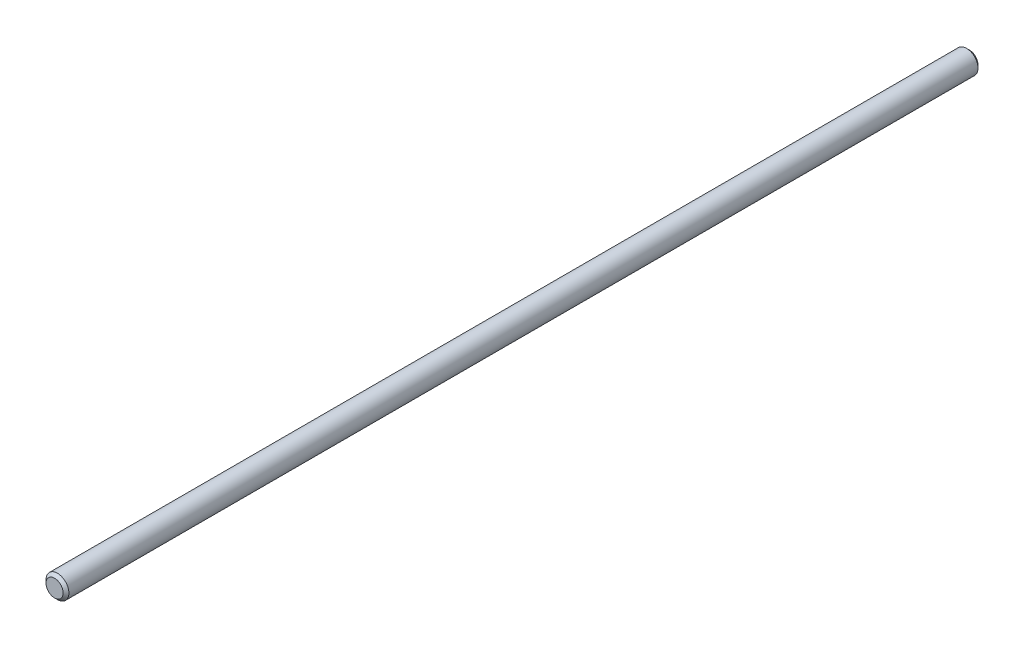
SolidWorks part; units mm, degrees
ref_plane "Piano frontale" through (0, 0, 0) normal (0, 0, 1) x (1, 0, 0)
ref_plane "Piano superiore" through (0, 0, 0) normal (0, 1, 0) x (1, 0, 0)
ref_plane "Piano destro" through (0, 0, 0) normal (1, 0, 0) x (0, 0, -1)
sketch "Schizzo1" plane through (0, 0, 0) normal (0, 0, 1) x (1, 0, 0)
  circle A0 centre (0, 0) radius 4
  dimension "D1" = 8
extrude "Estrusione-Estrusione1" add sketch "Schizzo1" along normal blind 320
chamfer "Smusso1" distance 1 angle 45 2 edges at (4, 0, 320) (4, 0, 0)
